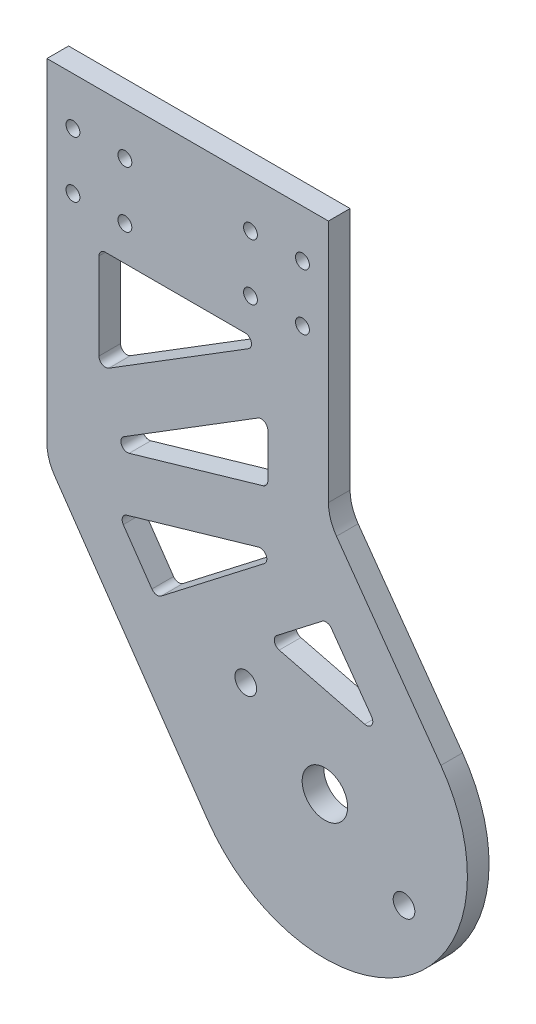
SolidWorks part; units mm, degrees
material "Thornel Mat VMA"
ref_plane "前视基准面" through (0, 0, 0) normal (0, 0, 1) x (1, 0, 0)
ref_plane "上视基准面" through (0, 0, 0) normal (0, 1, 0) x (1, 0, 0)
ref_plane "右视基准面" through (0, 0, 0) normal (1, 0, 0) x (0, 0, -1)
sketch "草图1" plane through (0, 0, 0) normal (0, 0, 1) x (1, 0, 0)
  line L0 (-34.1824, 86) -> (30.8176, 86) construction
  line L1 (-40, 86) -> (40, 86)
  line L2 (-40, 86) -> (-40, -44)
  line L3 (-40, -44) -> (40, -44)
  line L4 (40, 86) -> (40, -44)
  circle A0 centre (30, -29) radius 5.25
  dimension "D1" = 10.5
  dimension "D3" = 10
  dimension "D4" = 130
  dimension "D5" = 15
  dimension "D2" = 80
extrude "凸台-拉伸1" add sketch "草图1" against normal blind 5
sketch "Sketch1" plane through (0, 0, 0) normal (0, 0, 1) x (1, 0, 0)
  line L0 (40, 21) -> (61.0932, -36.953)
  line L1 (40, -44) -> (40, 86) construction
  line L2 (61.0932, -36.953) -> (61.0932, -54.953)
  line L3 (61.0932, -54.953) -> (43.0932, -54.953)
  line L4 (43.0932, -54.953) -> (13, -44)
  line L5 (-40, -44) -> (40, -44) construction
  line L6 (48.271, -42.1309) -> (30, -29) construction
  line L7 (61.0932, -54.953) -> (-4.9021, 11.0422) construction
  line L8 (13, -44) -> (40, -44)
  line L9 (40, -44) -> (40, 21)
  line L10 (48.271, -42.1309) -> (30, -29) construction
  circle A1 centre (48.271, -42.1309) radius 2.5
  dimension "D8" = 5
  dimension "D1" = 45
  dimension "D2" = 160
  dimension "D3" = 160
  dimension "D4" = 22.5
  dimension "D5" = 27
  dimension "D6" = 65
  dimension "D7" = 18
  dimension "D9" = 22.5
extrude "Extrude1" add sketch "Sketch1" against normal blind 5
sketch "Sketch2" plane through (0, 0, -5) normal (0, 0, -1) x (-1, 0, 0)
  line L0 (-3.3776, -47.6412) -> (34.1824, 6)
  line L1 (34.1824, 6) -> (34.1824, 86)
  line L2 (-40, 86) -> (40, 86) construction
  line L3 (-30.8176, 86) -> (34.1824, 86) construction
  line L4 (-30.8176, 86) -> (-30.8176, 26.4944)
  line L5 (34.1824, 86) -> (40, 86)
  line L6 (40, 86) -> (40, -82.8374)
  line L7 (40, -82.8374) -> (-89.511, -82.8374)
  line L8 (-89.511, -82.8374) -> (-89.511, 86.8079)
  line L9 (-89.511, 86.8079) -> (-30.8176, 86)
  line L10 (-30.8176, 26.4944) -> (-56.6224, -10.3588)
  arc A0 (-56.6224, -10.3588) -> (-3.3776, -47.6412) centre (-30, -29) ccw
  dimension "D2" = 65
  dimension "D1" = 65
  dimension "D3" = 65
  dimension "D4" = 80
  dimension "D5" = 145
extrude "Cut-Extrude1" cut sketch "Sketch2" against normal blind 10
sketch "Sketch3" plane through (0, 0, -5) normal (0, 0, -1) x (-1, 0, 0)
  line L0 (-30.8176, 26.4944) -> (-56.7849, -9.8768)
  line L1 (34.1824, 6) -> (-2.9228, -47.7071)
  line L2 (34.1824, 86) -> (34.1824, 6) construction
  line L3 (-30.8176, 26.4944) -> (34.1824, 6)
  arc A0 (-56.7849, -9.8768) -> (-2.9228, -47.7071) centre (-30, -29) ccw
  circle A2 centre (-48.271, -42.1309) radius 2.7605
  circle A3 centre (-30, -29) radius 5.25 construction
  circle A4 centre (-30, -29) radius 5.25
extrude "Extrude2" add sketch "Sketch3" against normal blind 5
sketch "Sketch4" plane through (0, 0, -5) normal (0, 0, -1) x (-1, 0, 0)
  circle A0 centre (-11.729, -15.8691) radius 2.5
  dimension "D1" = 5
extrude "Cut-Extrude2" cut sketch "Sketch4" against normal blind 5
fillet "Fillet1" radius 10 2 edges at (30.8176, 26.4944, -2.5) (-34.1824, 6, -2.5)
sketch "Sketch5" plane through (0, 0, 0) normal (0, 0, 1) x (1, 0, 0)
  circle A0 centre (24.8176, 62) radius 1.6 construction
  circle A1 centre (12.8176, 62) radius 1.6 construction
  circle A2 centre (24.8176, 75) radius 1.6 construction
  circle A3 centre (12.8176, 75) radius 1.6 construction
  circle A4 centre (-16.1824, 62) radius 1.6 construction
  circle A5 centre (-16.1824, 75) radius 1.6 construction
  circle A6 centre (-28.1824, 62) radius 1.6 construction
  circle A7 centre (-28.1824, 75) radius 1.6 construction
  circle A8 centre (24.8176, 62) radius 1.6
  circle A9 centre (12.8176, 62) radius 1.6
  circle A10 centre (24.8176, 75) radius 1.6
  circle A11 centre (12.8176, 75) radius 1.6
  circle A12 centre (-16.1824, 62) radius 1.6
  circle A13 centre (-16.1824, 75) radius 1.6
  circle A14 centre (-28.1824, 62) radius 1.6
  circle A15 centre (-28.1824, 75) radius 1.6
extrude "Cut-Extrude3" cut sketch "Sketch5" against normal blind 10
sketch "Sketch6" plane through (0, 0, -5) normal (0, 0, -1) x (-1, 0, 0)
  line L0 (-11.556, 54) -> (20.6824, 54)
  line L1 (22.1824, 52.5) -> (22.1824, 32.4924)
  line L2 (19.8915, 31.2179) -> (-12.347, 51.2255)
  line L3 (-14.5266, 38.4551) -> (16.4063, 19.2577)
  line L4 (15.1974, 16.5426) -> (-15.7355, 25.5171)
  line L5 (-16.8176, 26.9577) -> (-16.8176, 37.1806)
  line L9 (-32.679, 23.8873) -> (-56.7849, -9.8768) construction
  line L10 (-30.8176, 29.6979) -> (-30.8176, 86) construction
  line L11 (-14.6772, 12.7152) -> (15.7392, 3.8906)
  line L12 (-15.8434, -26.8236) -> (-28.3802, 54.7216) construction
  line L13 (34.1824, 86) -> (34.1824, 9.1185) construction
  line L14 (16.5554, 1.5974) -> (9.9445, -7.9714)
  line L15 (7.7932, -8.3058) -> (-16.0122, 10.0876)
  line L16 (-31.4835, 4.9097) -> (-40.7814, -8.1134)
  line L17 (-39.1954, -10.4398) -> (-19.4564, -5.4841)
  line L18 (-18.9045, -2.8423) -> (-29.3456, 5.2251)
  line L19 (-2.9228, -47.7071) -> (32.4098, 3.4343) construction
  circle A0 centre (16.1824, 62) radius 1.6 construction
  arc A1 (-11.556, 54) -> (-12.347, 51.2255) centre (-11.556, 52.5) ccw
  arc A2 (20.6824, 54) -> (22.1824, 52.5) centre (20.6824, 52.5) cw
  arc A3 (22.1824, 32.4924) -> (19.8915, 31.2179) centre (20.6824, 32.4924) cw
  arc A4 (-14.5266, 38.4551) -> (-16.8176, 37.1806) centre (-15.3176, 37.1806) ccw
  arc A5 (16.4063, 19.2577) -> (15.1974, 16.5426) centre (15.6153, 17.9832) cw
  arc A6 (-15.7355, 25.5171) -> (-16.8176, 26.9577) centre (-15.3176, 26.9577) cw
  arc A7 (-40.7814, -8.1134) -> (-39.1954, -10.4398) centre (-39.5607, -8.985) ccw
  arc A8 (-31.4835, 4.9097) -> (-29.3456, 5.2251) centre (-30.2628, 4.0381) cw
  arc A9 (-19.4564, -5.4841) -> (-18.9045, -2.8423) centre (-19.8216, -4.0293) ccw
  arc A10 (-14.6772, 12.7152) -> (-16.0122, 10.0876) centre (-15.0951, 11.2746) ccw
  arc A11 (9.9445, -7.9714) -> (7.7932, -8.3058) centre (8.7104, -7.1188) cw
  arc A12 (15.7392, 3.8906) -> (16.5554, 1.5974) centre (15.3212, 2.45) cw
  point P14 (-21.5337, 10.1889)
  point P21 (0, 0)
  point P26 (20.6637, 17.312)
  point P27 (17.7664, 16.3201)
  point P28 (-16.8176, 28.9838)
  point P31 (-16.8176, 54)
  point P40 (25.6831, 13.5004)
  point P43 (0, 0)
  point P44 (-16.8176, 28.9838)
  point P45 (-22.6723, 17.5946)
  point P46 (0, 0)
  point P47 (17.7389, 3.3104)
  point P56 (-22.2604, 14.9153)
  dimension "D6" = 1.5
  dimension "D10" = 1.5
  dimension "D1" = 12
  dimension "D2" = 14
  dimension "D3" = 12
  dimension "D4" = 12
  dimension "D5" = 12
  dimension "D7" = 8
  dimension "D8" = 12
  dimension "D9" = 12
extrude "Cut-Extrude4" cut sketch "Sketch6" against normal blind 18
